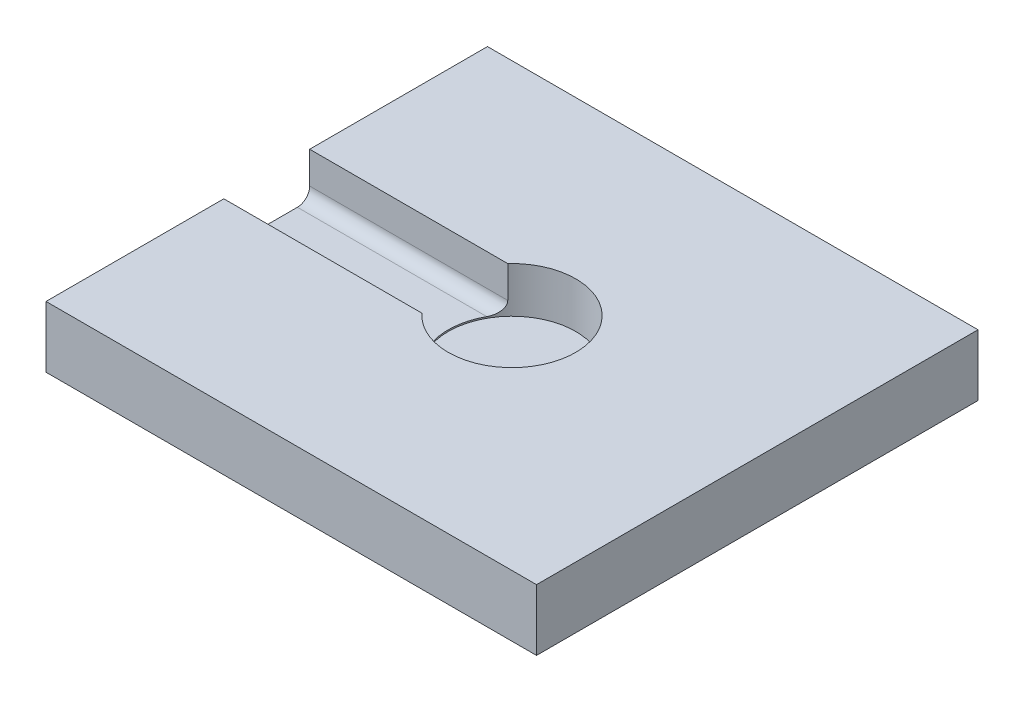
SolidWorks part; units mm, degrees
ref_plane "Front Plane" through (0, 0, 0) normal (0, 0, 1) x (1, 0, 0)
ref_plane "Top Plane" through (0, 0, 0) normal (0, 1, 0) x (1, 0, 0)
ref_plane "Right Plane" through (0, 0, 0) normal (1, 0, 0) x (0, 0, -1)
sketch "Sketch1" plane through (0, 0, 0) normal (0, 1, 0) x (1, 0, 0)
  line L1 (100, 90) -> (-100, 90)
  line L2 (100, 90) -> (100, -90)
  line L3 (100, -90) -> (-100, -90)
  line L4 (-100, 90) -> (-100, -90)
  line L5 (100, 90) -> (-100, -90) construction
  line L6 (100, -90) -> (-100, 90) construction
  point P0 (0, 0)
  dimension "D1" = 180
  dimension "D2" = 200
extrude "base" add sketch "Sketch1" along normal blind 25
sketch "Sketch2" plane through (0, 25, 0) normal (0, 1, 0) x (1, 0, 0)
  circle A0 centre (0, 0) radius 26
  dimension "D1" = 52
extrude "load cell cut" cut sketch "Sketch2" against normal blind 18.6 contours A0
sketch "Sketch3" plane through (-100, 0, 0) normal (1, 0, 0) x (0, 0, -1)
  line L1 (-17.5, 7) -> (17.5, 7)
  line L2 (-17.5, 7) -> (-17.5, 25)
  line L3 (-17.5, 25) -> (17.5, 25)
  line L4 (17.5, 7) -> (17.5, 25)
  line L5 (-90, 25) -> (90, 25) construction
  line L6 (-90, 0) -> (90, 0) construction
  point P6 (0, 7)
  point P10 (0, 0)
  dimension "D1" = 18
  dimension "D2" = 35
extrude "wire cut" cut sketch "Sketch3" along normal up to next
fillet "wire cut fillet" radius 5 2 edges at (-59.6144, 7, 17.5) (-59.6144, 7, -17.5)
sketch "Sketch4" plane through (0, 25, 0) normal (0, 1, 0) x (1, 0, 0)
  line L0 (-100, -17.5) -> (-100, -90) construction
  line L1 (-100, -90) -> (100, -90) construction
  line L2 (100, -90) -> (100, 90) construction
  line L3 (100, 90) -> (-100, 90) construction
  point P0 (-80, -70)
  point P6 (-80, 70)
  point P7 (80, 70)
  point P8 (80, -70)
  dimension "D1" = 20
  dimension "D2" = 20
  dimension "D3" = 20
  dimension "D4" = 20
equation "\"D2@Sketch4\"=\"D1@Sketch4\""
equation "\"D3@Sketch4\"=\"D1@Sketch4\""
equation "\"D4@Sketch4\"=\"D1@Sketch4\""
